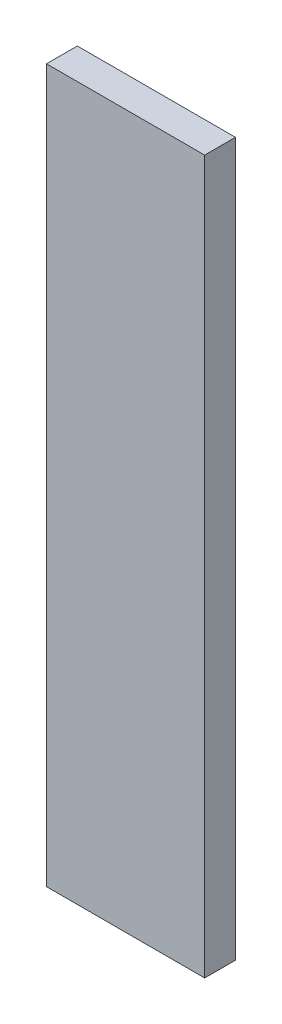
SolidWorks part; units mm, degrees
ref_plane "Front Plane" through (0, 0, 0) normal (0, 0, 1) x (1, 0, 0)
ref_plane "Top Plane" through (0, 0, 0) normal (0, 1, 0) x (1, 0, 0)
ref_plane "Right Plane" through (0, 0, 0) normal (1, 0, 0) x (0, 0, -1)
sketch "Sketch1" plane through (0, 0, 0) normal (0, 0, 1) x (1, 0, 0)
  line L0 (0, 3.5) -> (0, 3) construction
  line L1 (3, 3) -> (-3, 3)
  line L2 (3, 3) -> (3, -3)
  line L3 (3, -3) -> (-3, -3)
  line L4 (-3, 3) -> (-3, -3)
  line L5 (3, 3) -> (-3, -3) construction
  line L6 (3, -3) -> (-3, 3) construction
  line L7 (2, 3.5) -> (-2, 3.5) construction
  line L8 (0, 3) -> (0, 2.5) construction
  line L9 (-2, 2.5) -> (2, 2.5) construction
  line L10 (-2.5, 0) -> (-3, 0) construction
  line L11 (-2.5, -2) -> (-2.5, 2) construction
  line L12 (-3, 0) -> (-3.5, 0) construction
  line L13 (-3.5, 2) -> (-3.5, -2) construction
  point P0 (0, 0)
extrude "Extrude-Thin1" add sketch "Sketch1" against normal blind 4 thin thin type mid plane wall 0.8
pattern_linear "LPattern1" count 5 spacing 6 along (-1, 0, 0) count 23 spacing 6 along (0, 1, 0) of "Extrude-Thin1"
sketch "Sketch2" plane through (0, 0, 0) normal (0, 0, 1) x (1, 0, 0)
  line L1 (3.4, -3.4) -> (-27.4, -3.4)
  line L2 (3.4, -3.4) -> (3.4, 135.4)
  line L3 (3.4, 135.4) -> (-27.4, 135.4)
  line L4 (-27.4, -3.4) -> (-27.4, 135.4)
  line L5 (3.4, -3.4) -> (-27.4, 135.4) construction
  line L6 (3.4, 135.4) -> (-27.4, -3.4) construction
  point P4 (-12, 66)
  point P6 (-27.833, 124.5993)
  point P7 (-24.95, 123.95)
extrude "Boss-Extrude1" add sketch "Sketch2" along normal blind 2
